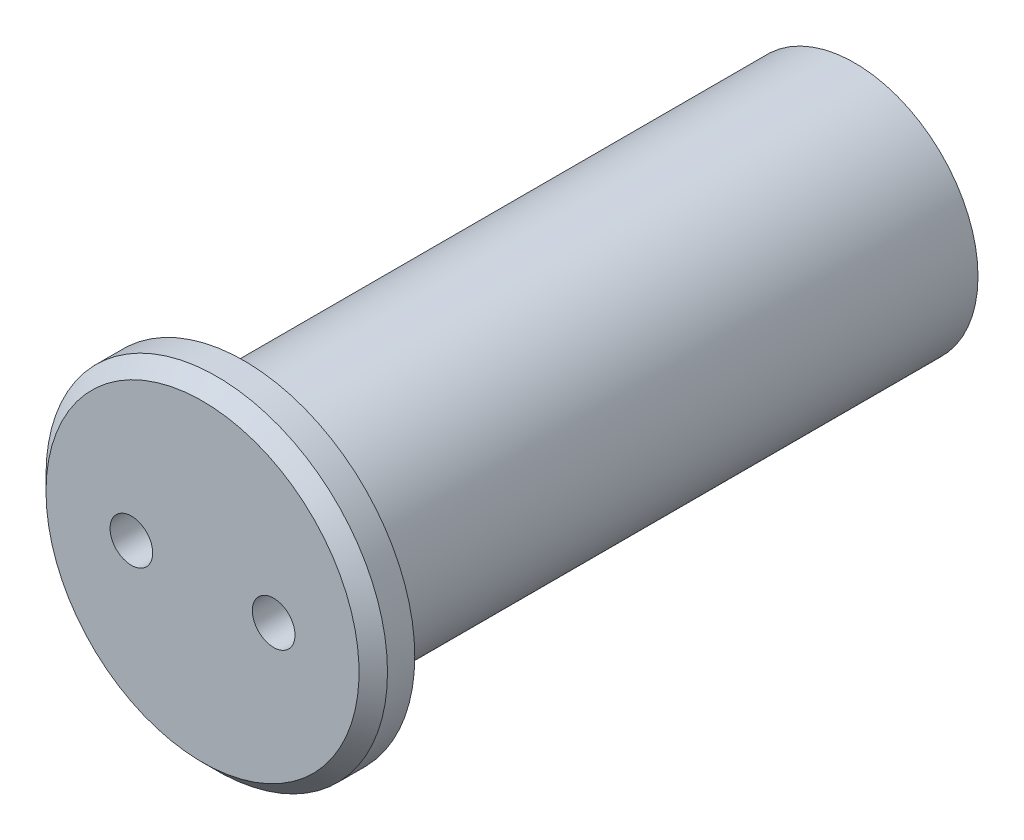
SolidWorks part; units mm, degrees
ref_plane "前视基准面" through (0, 0, 0) normal (0, 0, 1) x (1, 0, 0)
ref_plane "上视基准面" through (0, 0, 0) normal (0, 1, 0) x (1, 0, 0)
ref_plane "右视基准面" through (0, 0, 0) normal (1, 0, 0) x (0, 0, -1)
sketch "草图1" plane through (0, 0, 0) normal (0, 0, 1) x (1, 0, 0)
  circle A0 centre (0, 0) radius 5.2
extrude "凸台-拉伸1" add sketch "草图1" along normal blind 27.5
ref_plane "基准面4" through (0, 0, 13.75) normal (0, 0, 1) x (1, 0, 0)
sketch "草图3" plane through (0, 0, 27.5) normal (0, 0, 1) x (1, 0, 0)
  line L0 (0, 0) -> (0, 5.6384) construction
  circle A0 centre (-3, 0) radius 0.85
  circle A1 centre (3, 0) radius 0.85
  point P9 (0, 0)
  dimension "D1" = 1.7
  dimension "D2" = 3
  dimension "D3" = 2
sketch "草图6" plane through (0, 0, 27.5) normal (0, 0, 1) x (1, 0, 0)
  circle A0 centre (0, 0) radius 7.2
extrude "凸台-拉伸3" add sketch "草图6" against normal blind 1.75
extrude "切除-拉伸4" cut sketch "草图3" against normal blind 8
mirror "镜向3" about plane through (0, 0, 13.75) normal (0, 0, 1) of "切除-拉伸4"
sketch "草图7" plane through (0, 0, 27.5) normal (0, 0, 1) x (1, 0, 0)
  circle A0 centre (-3, 0) radius 0.9
  circle A1 centre (3, 0) radius 0.9
extrude "切除-拉伸5" cut sketch "草图7" against normal up to surface (8 mm away) up to face at (-2.15, 0, 19.5)
chamfer "倒角1" distance 1 angle 45 2 edges at (-2.15, 0, 0) (3.85, 0, 0)
chamfer "倒角2" distance 0.6 angle 45 1 edges at (7.2, 0, 27.5)
